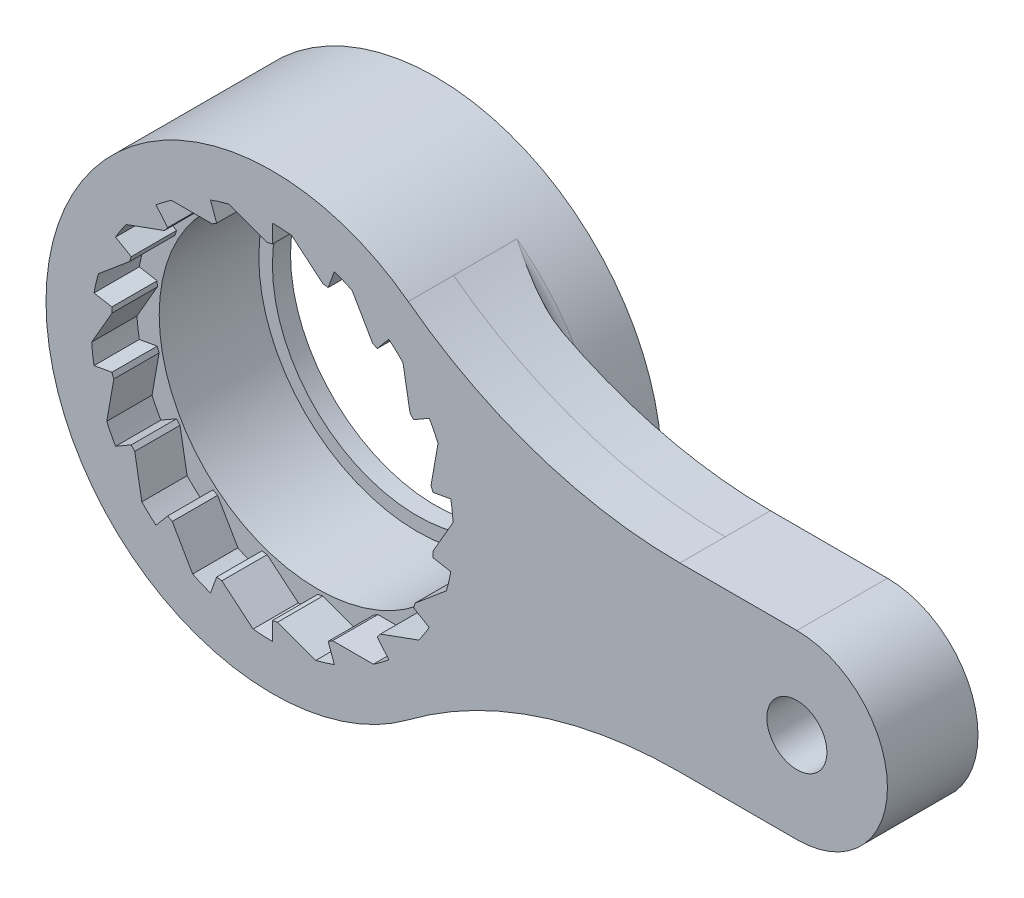
SolidWorks part; units mm, degrees
ref_plane "前视基准面" through (0, 0, 0) normal (0, 0, 1) x (1, 0, 0)
ref_plane "上视基准面" through (0, 0, 0) normal (0, 1, 0) x (1, 0, 0)
ref_plane "右视基准面" through (0, 0, 0) normal (1, 0, 0) x (0, 0, -1)
sketch "草图15" plane through (0, 0, 0) normal (0, 0, 1) x (1, 0, 0)
  line L0 (-50, 0) -> (150, 0) construction
  line L2 (-27.0871, 10) -> (72.9129, 10)
  line L4 (-27.0871, -10) -> (72.9129, -10)
  arc A0 (-27.0871, 10) -> (-27.0871, -10) centre (-50, 0) ccw
  arc A1 (72.9129, -10) -> (72.9129, 10) centre (72.9129, 0) ccw
  circle A2 centre (-50, 0) radius 20
  circle A3 centre (72.9129, 0) radius 4
  dimension "D2" = 50
  dimension "D7" = 8
  dimension "D6" = 40
  dimension "D1" = 200
  dimension "D3" = 20
  dimension "D4" = 10
  dimension "D5" = 50
extrude "凸台-拉伸10" add sketch "草图15" along normal blind 5
fillet "圆角1" radius 50 2 edges at (-27.0871, -10, 2.5) (-27.0871, 10, 2.5)
sketch "草图16" plane through (0, 0, 0) normal (0, 0, -1) x (-1, 0, 0)
  circle A0 centre (50, 0) radius 25
  circle A1 centre (50, 0) radius 20
extrude "凸台-拉伸11" add sketch "草图16" along normal blind 5
sketch "草图17" plane through (0, 0, -5) normal (0, 0, -1) x (-1, 0, 0)
  circle A0 centre (50, 0) radius 20
extrude "凸台-拉伸12" add sketch "草图17" against normal blind 5
sketch "草图18" plane through (0, 0, -5) normal (0, 0, -1) x (-1, 0, 0)
  circle A0 centre (50, 0) radius 7.5
  dimension "D1" = 15
extrude "切除-拉伸5" cut sketch "草图18" against normal blind 5
sketch "草图19" plane through (0, 0, 0) normal (0, 0, 1) x (1, 0, 0)
  line L0 (-50, 28.8363) -> (-50, -30.3636) construction
  line L49 (-50, 20) -> (-50, 18)
  line L50 (-50, 20) -> (-48, 20)
  line L51 (-48, 20) -> (-44.417, 16.9935)
  line L52 (-43.1596, 18.7939) -> (-43.8436, 16.9145)
  line L53 (-43.1596, 18.7939) -> (-41.2802, 18.1098)
  line L54 (-41.2802, 18.1098) -> (-38.9416, 14.0592)
  line L55 (-37.1442, 15.3209) -> (-38.4298, 13.7888)
  line L56 (-37.1442, 15.3209) -> (-35.6122, 14.0353)
  line L57 (-35.6122, 14.0353) -> (-34.8, 9.4291)
  line L58 (-32.6795, 10) -> (-34.4115, 9)
  line L59 (-32.6795, 10) -> (-31.6795, 8.2679)
  line L60 (-31.6795, 8.2679) -> (-32.4917, 3.6617)
  line L61 (-30.3038, 3.473) -> (-32.2735, 3.1257)
  line L62 (-30.3038, 3.473) -> (-29.9565, 1.5033)
  line L63 (-29.9565, 1.5033) -> (-32.2952, -2.5473)
  line L64 (-30.3038, -3.473) -> (-32.2735, -3.1257)
  line L65 (-30.3038, -3.473) -> (-30.6511, -5.4426)
  line L66 (-30.6511, -5.4426) -> (-34.2341, -8.4491)
  line L67 (-32.6795, -10) -> (-34.4115, -9)
  line L68 (-32.6795, -10) -> (-33.6795, -11.7321)
  line L69 (-33.6795, -11.7321) -> (-38.0747, -13.3318)
  line L70 (-37.1442, -15.3209) -> (-38.4298, -13.7888)
  line L71 (-37.1442, -15.3209) -> (-38.6763, -16.6065)
  line L72 (-38.6763, -16.6065) -> (-43.3536, -16.6065)
  line L73 (-43.1596, -18.7939) -> (-43.8436, -16.9145)
  line L74 (-43.1596, -18.7939) -> (-45.039, -19.4779)
  line L75 (-45.039, -19.4779) -> (-49.4342, -17.8782)
  line L76 (-50, -20) -> (-50, -18)
  line L77 (-50, -20) -> (-52, -20)
  line L78 (-52, -20) -> (-55.583, -16.9935)
  line L79 (-56.8404, -18.7939) -> (-56.1564, -16.9145)
  line L80 (-56.8404, -18.7939) -> (-58.7198, -18.1098)
  line L81 (-58.7198, -18.1098) -> (-61.0584, -14.0592)
  line L82 (-62.8558, -15.3209) -> (-61.5702, -13.7888)
  line L83 (-62.8558, -15.3209) -> (-64.3878, -14.0353)
  line L84 (-64.3878, -14.0353) -> (-65.2, -9.4291)
  line L85 (-67.3205, -10) -> (-65.5885, -9)
  line L86 (-67.3205, -10) -> (-68.3205, -8.2679)
  line L87 (-68.3205, -8.2679) -> (-67.5083, -3.6617)
  line L88 (-69.6962, -3.473) -> (-67.7265, -3.1257)
  line L89 (-69.6962, -3.473) -> (-70.0435, -1.5033)
  line L90 (-70.0435, -1.5033) -> (-67.7048, 2.5473)
  line L91 (-69.6962, 3.473) -> (-67.7265, 3.1257)
  line L92 (-69.6962, 3.473) -> (-69.3489, 5.4426)
  line L93 (-69.3489, 5.4426) -> (-65.7659, 8.4491)
  line L94 (-67.3205, 10) -> (-65.5885, 9)
  line L95 (-67.3205, 10) -> (-66.3205, 11.7321)
  line L96 (-66.3205, 11.7321) -> (-61.9253, 13.3318)
  line L97 (-62.8558, 15.3209) -> (-61.5702, 13.7888)
  line L98 (-62.8558, 15.3209) -> (-61.3237, 16.6065)
  line L99 (-61.3237, 16.6065) -> (-56.6464, 16.6065)
  line L100 (-56.8404, 18.7939) -> (-56.1564, 16.9145)
  line L101 (-56.8404, 18.7939) -> (-54.961, 19.4779)
  line L102 (-54.961, 19.4779) -> (-50.5658, 17.8782)
  line L103 (-50.5658, 17.8782) -> (-50, 18)
  line L104 (-44.417, 16.9935) -> (-43.8436, 16.9145)
  line L105 (-38.9416, 14.0592) -> (-38.4298, 13.7888)
  line L106 (-34.8, 9.4291) -> (-34.4115, 9)
  line L107 (-32.4917, 3.6617) -> (-32.2735, 3.1257)
  line L108 (-32.2952, -2.5473) -> (-32.2735, -3.1257)
  line L109 (-34.2341, -8.4491) -> (-34.4115, -9)
  line L110 (-38.0747, -13.3318) -> (-38.4298, -13.7888)
  line L111 (-43.3536, -16.6065) -> (-43.8436, -16.9145)
  line L112 (-49.4342, -17.8782) -> (-50, -18)
  line L113 (-55.583, -16.9935) -> (-56.1564, -16.9145)
  line L114 (-61.0584, -14.0592) -> (-61.5702, -13.7888)
  line L115 (-65.2, -9.4291) -> (-65.5885, -9)
  line L116 (-67.5083, -3.6617) -> (-67.7265, -3.1257)
  line L117 (-67.7048, 2.5473) -> (-67.7265, 3.1257)
  line L118 (-65.7659, 8.4491) -> (-65.5885, 9)
  line L119 (-61.9253, 13.3318) -> (-61.5702, 13.7888)
  line L120 (-56.6464, 16.6065) -> (-56.1564, 16.9145)
  circle A0 centre (-50, 0) radius 25
  circle A25 centre (-50, 0) radius 20 construction
  point P80 (-50, 0)
  point P115 (-50, 0)
  dimension "D4" = 50
  dimension "D1" = 2
  dimension "D2" = 2
  dimension "D3" = 140
extrude "凸台-拉伸13" add sketch "草图19" along normal up to surface (5 mm away) up to face at (-30, 0, 5)
sketch "草图20" plane through (0, 0, -5) normal (0, 0, -1) x (-1, 0, 0)
  circle A0 centre (50, 0) radius 10
  dimension "D1" = 20
extrude "切除-拉伸6" cut sketch "草图20" against normal blind 5
sketch "草图21" plane through (0, 0, -5) normal (0, 0, -1) x (-1, 0, 0)
  circle A0 centre (50, 0) radius 17.5
  dimension "D1" = 35
extrude "切除-拉伸7" cut sketch "草图21" against normal blind 5
sketch "草图22" plane through (0, 0, -5) normal (0, 0, -1) x (-1, 0, 0)
  circle A0 centre (50, 0) radius 17.5
  circle A1 centre (50, 0) radius 25
  dimension "D1" = 35
  dimension "D2" = 50
extrude "凸台-拉伸14" add sketch "草图22" along normal blind 6
sketch "草图24" plane through (0, 0, -11) normal (0, 0, -1) x (-1, 0, 0)
  circle A0 centre (50, 0) radius 25
  circle A1 centre (50, 0) radius 16
  dimension "D1" = 32
extrude "凸台-拉伸16" add sketch "草图24" along normal blind 2
sketch "草图25" plane through (0, 0, 0) normal (0, 0, -1) x (-1, 0, 0)
  line L0 (-72.9129, 10) -> (5, 10)
  line L1 (-72.9129, -10) -> (5, -10)
  line L2 (5, 10) -> (27.0871, 10)
  line L3 (5, -10) -> (27.0871, -10)
  circle A0 centre (-72.9129, 0) radius 4
  arc A1 (-72.9129, 10) -> (-72.9129, -10) centre (-72.9129, 0) ccw
  circle A2 centre (50, 0) radius 25 construction
  arc A3 (27.0871, 10) -> (27.0871, -10) centre (50, 0) ccw
extrude "凸台-拉伸17" add sketch "草图25" along normal blind 5
fillet "圆角2" radius 50 2 edges at (-27.0871, -10, -2.5) (-27.0871, 10, -2.5)
sketch "草图26" plane through (0, 0, -5) normal (0, 0, -1) x (-1, 0, 0)
  line L0 (-93.6526, 0) -> (43.9133, 0) construction
  line L1 (-42.9129, 10) -> (-101.4602, 10)
  line L2 (-101.4602, 10) -> (-101.4602, -10)
  line L3 (-42.9129, -10) -> (-101.4602, -10)
  arc A0 (-42.9129, 10) -> (-42.9129, -10) centre (-42.9129, 0) ccw
  point P6 (-72.9129, 0)
extrude "切除-拉伸8" cut sketch "草图26" against normal blind 10
sketch "草图27" plane through (0, 0, -5) normal (0, 0, -1) x (-1, 0, 0)
  circle A0 centre (-42.9129, 0) radius 4
  dimension "D1" = 8
extrude "切除-拉伸9" cut sketch "草图27" against normal blind 10
fillet "圆角3" radius 2 1 edges at (-25, 0, -5)
sketch "草图28" plane through (0, 0, -5) normal (0, 0, -1) x (-1, 0, 0)
  line L0 (-60.0886, 0) -> (97.6913, 0) construction
  circle A0 centre (-7.9129, 0) radius 3.3153
  point P5 (-42.9129, 0)
  dimension "D1" = 35
extrude "切除-拉伸10" cut sketch "草图28" against normal through all
sketch "草图29" plane through (0, 0, -5) normal (0, 0, -1) x (-1, 0, 0)
  line L0 (-7.9129, 10) -> (-73.9304, 10)
  line L1 (-73.9304, 10) -> (-73.9304, -10)
  line L2 (-73.9304, -10) -> (-7.9129, -10)
  arc A0 (-7.9129, 10) -> (-7.9129, -10) centre (-7.9129, 0) ccw
extrude "切除-拉伸11" cut sketch "草图29" against normal through all
